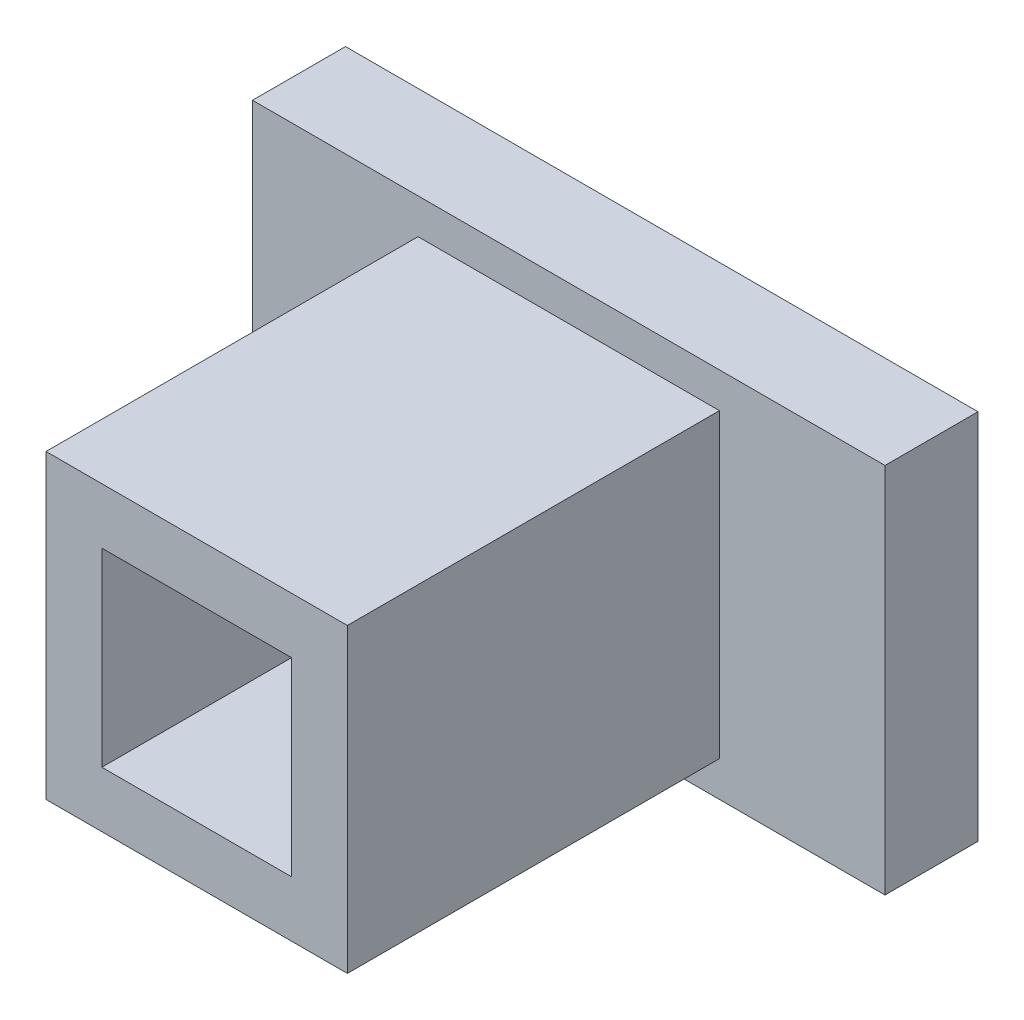
SolidWorks part; units mm, degrees
ref_plane "前视基准面" through (0, 0, 0) normal (0, 0, 1) x (1, 0, 0)
ref_plane "上视基准面" through (0, 0, 0) normal (0, 1, 0) x (1, 0, 0)
ref_plane "右视基准面" through (0, 0, 0) normal (1, 0, 0) x (0, 0, -1)
other "Configuration Table"
sketch "草图1" plane through (0, 0, 0) normal (0, 0, 1) x (1, 0, 0)
  line L5 (-17, -10) -> (17, -10)
  line L6 (-17, -10) -> (-17, 10)
  line L7 (-17, 10) -> (17, 10)
  line L8 (17, -10) -> (17, 10)
  line L9 (-17, -10) -> (17, 10) construction
  line L10 (-17, 10) -> (17, -10) construction
  line L11 (-5.1, -5.1) -> (5.1, -5.1)
  line L12 (-5.1, -5.1) -> (-5.1, 5.1)
  line L13 (-5.1, 5.1) -> (5.1, 5.1)
  line L14 (5.1, -5.1) -> (5.1, 5.1)
  line L15 (-5.1, -5.1) -> (5.1, 5.1) construction
  line L16 (-5.1, 5.1) -> (5.1, -5.1) construction
  line L17 (-8.1, -8.1) -> (8.1, -8.1)
  line L18 (-8.1, -8.1) -> (-8.1, 8.1)
  line L19 (-8.1, 8.1) -> (8.1, 8.1)
  line L20 (8.1, -8.1) -> (8.1, 8.1)
  line L21 (-8.1, -8.1) -> (8.1, 8.1) construction
  line L22 (-8.1, 8.1) -> (8.1, -8.1) construction
  point P0 (0, 0)
  point P13 (0, 0)
  dimension "D4" = 34
  dimension "D1" = 10.2
  dimension "D2" = 3
  dimension "D3" = 20
extrude "凸台-拉伸1" add sketch "草图1" along normal blind 20 contours L18 L19 L20 L17 | L12 L13 L14 L11
extrude "凸台-拉伸2" add sketch "草图1<6>" against normal blind 5 contours L7 L8 L5 L6
sketch "草图1<6>" plane through (0, 0, 0) normal (0, 0, 1) x (1, 0, 0) same geometry as "草图1"
